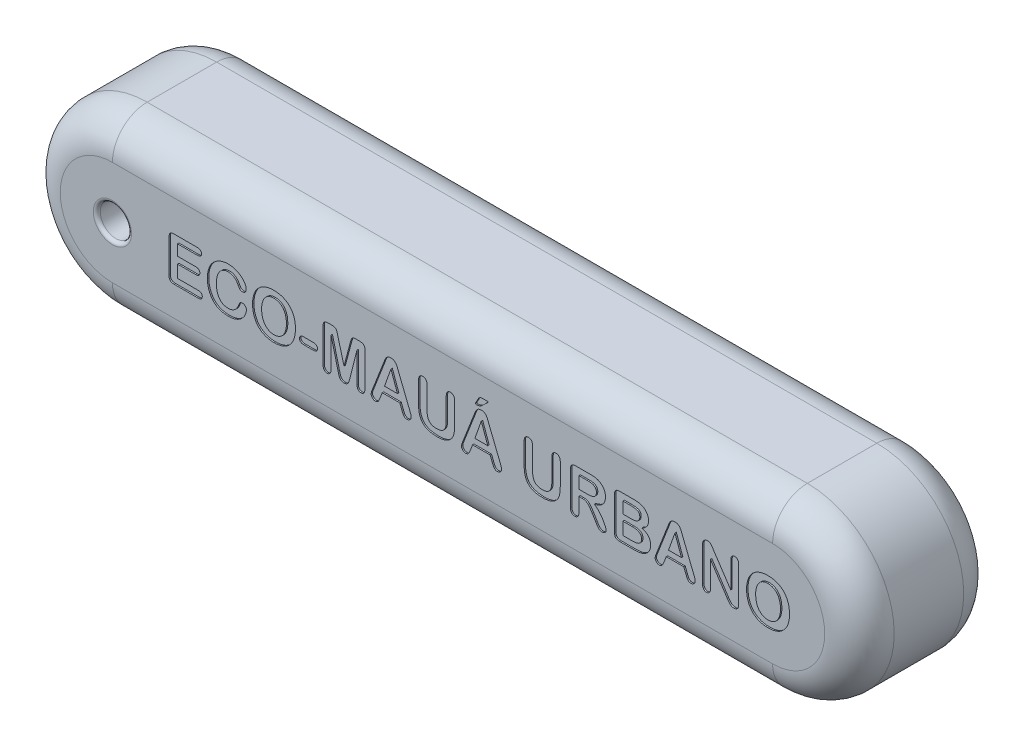
SolidWorks part; units mm, degrees
ref_plane "Front Plane" through (0, 0, 0) normal (0, 0, 1) x (1, 0, 0)
ref_plane "Top Plane" through (0, 0, 0) normal (0, 1, 0) x (1, 0, 0)
ref_plane "Right Plane" through (0, 0, 0) normal (1, 0, 0) x (0, 0, -1)
sketch "Sketch1" plane through (0, 0, 0) normal (0, 0, 1) x (1, 0, 0)
  line L0 (-12.5, 12.5) -> (107.5, -12.5) construction
  line L1 (-12.5, 12.5) -> (107.5, 12.5)
  line L2 (-12.5, 12.5) -> (-12.5, -12.5)
  line L3 (-12.5, -12.5) -> (107.5, -12.5)
  line L4 (107.5, 12.5) -> (107.5, -12.5)
  line L5 (0, 0) -> (47.5, 0) construction
  circle A0 centre (0, 0) radius 12.5
  circle A1 centre (95, 0) radius 12.5
  dimension "D1" = 120
  dimension "D2" = 25
extrude "Boss-Extrude1" add sketch "Sketch1" along normal blind 20 contours A0 L3 L4 L1 | A0 | A1 region at (47.5, 0, 0) region at (0, 0, 0) region at (95, 0, 0)
sketch "Sketch2" plane through (0, 0, 20) normal (0, 0, 1) x (1, 0, 0)
  line L0 (-5.5902, 5) -> (5.5902, 5)
  line L1 (0, 5) -> (0, -5) construction
  line L2 (5.5902, -5) -> (-5.5902, -5)
  circle A0 centre (0, 0) radius 7.5
  dimension "D1" = 15
  dimension "D2" = 10
extrude "Cut-Extrude1" cut sketch "Sketch2" against normal through all contours L0 L1 L2 A0 | L1 L0 A0 L2 region at (-3.4723, 0, 20) region at (3.4723, 0, 20)
fillet "Fillet3" radius 5 8 edges at (-12.5, 0, 20) (47.5, -12.5, 20) (107.5, 0, 20) (-12.5, 0, 0) (47.5, -12.5, 0) (107.5, 0, 0) (47.5, 12.5, 20) (47.5, 12.5, 0)
sketch "Sketch3" plane through (0, 0, 20) normal (0, 0, 1) x (1, 0, 0)
  circle A0 centre (0, 0) radius 7.5
  arc A1 (5.5902, -5) -> (5.5902, 5) centre (0, 0) ccw construction
  circle A2 centre (0, 0) radius 2.25
  dimension "D1" = 4.5
extrude "Boss-Extrude2" add sketch "Sketch3" against normal blind 5
fillet "Fillet4" radius 0.5 6 edges at (-7.5, 0, 0) (0, 5, 0) (0, -5, 0) (7.5, 0, 0) (2.25, 0, 15) (2.25, 0, 20)
sketch "Sketch4" plane through (0, 0, 20) normal (0, 0, 1) x (1, 0, 0)
  line L0 (2.75, 0) -> (102.5, 0) construction
  line L1 (2.75, 0) -> (2.75, -7.5) construction
  line L2 (0, -7.5) -> (95, -7.5) construction
  line L3 (102.5, 0) -> (102.5, -10) construction
  line L4 (2.75, -3.25) -> (102.5, -3.25) construction
  circle A0 centre (0, 0) radius 2.75 construction
  arc A1 (95, -7.5) -> (95, 7.5) centre (95, 0) ccw construction
  arc A2 (95, -12.5) -> (95, 12.5) centre (95, 0) ccw construction
  text T0 "ECO-MAUÁ URBANO" font "Arial Rounded MT Bold" height 6.5
  point P17 (0, 0)
  point P18 (102.5, -6.692)
  dimension "D1" = 3.25
extrude "Cut-Extrude2" cut sketch "Sketch4" against normal blind 0.2
